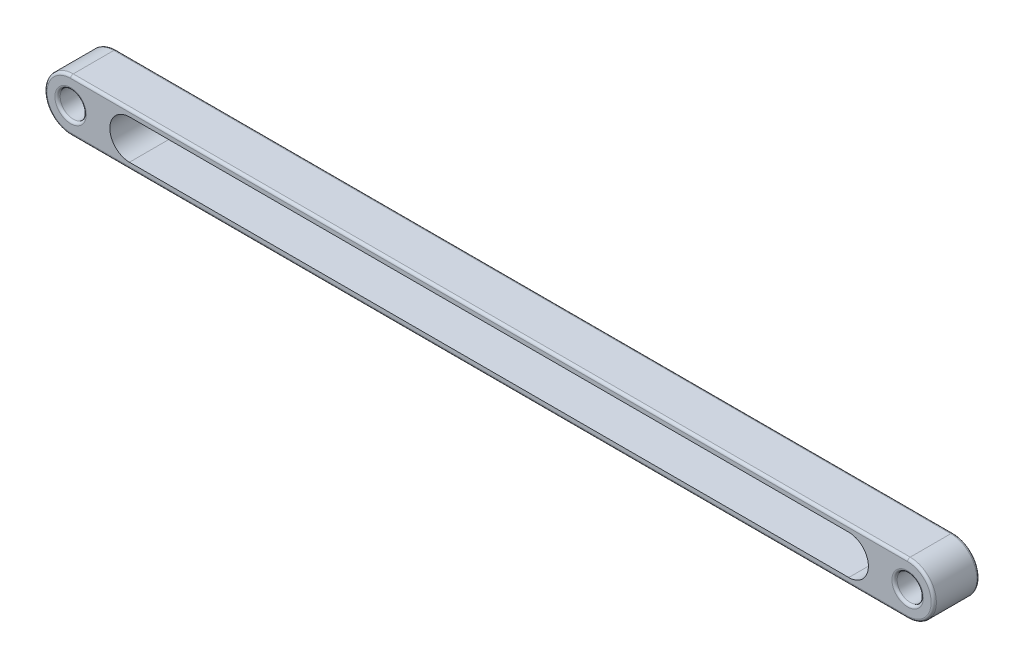
SolidWorks part; units mm, degrees
ref_plane "Front Plane" through (0, 0, 0) normal (0, 0, 1) x (1, 0, 0)
ref_plane "Top Plane" through (0, 0, 0) normal (0, 1, 0) x (1, 0, 0)
ref_plane "Right Plane" through (0, 0, 0) normal (1, 0, 0) x (0, 0, -1)
sketch "Sketch4" plane through (0, 0, 0) normal (0, 0, 1) x (1, 0, 0)
  line L0 (-320, 0) -> (320, 0) construction
  line L1 (-320, 20) -> (320, 20)
  line L2 (-320, -20) -> (320, -20)
  arc A0 (-320, 20) -> (-320, -20) centre (-320, 0) ccw
  arc A1 (320, -20) -> (320, 20) centre (320, 0) ccw
  point P3 (0, 0)
  dimension "D1" = 640
  dimension "D2" = 40
extrude "Boss-Extrude2" add sketch "Sketch4" along normal mid plane 35
sketch "Sketch5" plane through (0, 0, 17.5) normal (0, 0, 1) x (1, 0, 0)
  circle A0 centre (320, 0) radius 10
  circle A1 centre (-320, 0) radius 10
  dimension "D1" = 20
extrude "Cut-Extrude1" cut sketch "Sketch5" against normal through all
sketch "Sketch6" plane through (0, 0, -17.5) normal (0, 0, -1) x (-1, 0, 0)
  line L0 (-275, 0) -> (275, 0) construction
  line L1 (320, 0) -> (-320, 0) construction
  line L2 (-275, 15) -> (275, 15)
  line L3 (-275, -15) -> (275, -15)
  arc A0 (-275, 15) -> (-275, -15) centre (-275, 0) ccw
  arc A1 (275, -15) -> (275, 15) centre (275, 0) ccw
  point P4 (0, 0)
  dimension "D1" = 15
  dimension "D2" = 45
extrude "Cut-Extrude2" cut sketch "Sketch6" against normal blind 40
fillet "Fillet1" radius 2 12 edges at (340, 0, 17.5) (0, -20, 17.5) (-340, 0, 17.5) (340, 0, -17.5) (0, -20, -17.5) (-340, 0, -17.5) (0, 20, 17.5) (0, 20, -17.5) (330, 0, 17.5) (330, 0, -17.5) (-310, 0, 17.5) (-310, 0, -17.5)
